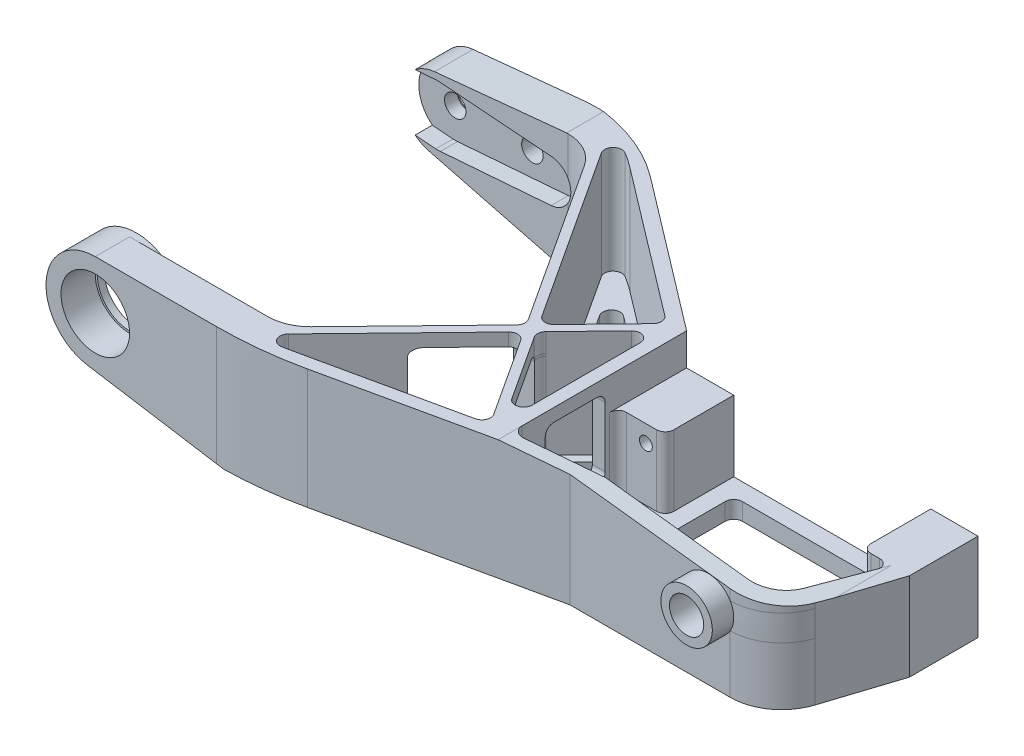
SolidWorks part; units mm, degrees
material "ABS"
ref_plane "Front Plane" through (0, 0, 0) normal (0, 0, 1) x (1, 0, 0)
ref_plane "Top Plane" through (0, 0, 0) normal (0, 1, 0) x (1, 0, 0)
ref_plane "Right Plane" through (0, 0, 0) normal (1, 0, 0) x (0, 0, -1)
sketch "Sketch1" plane through (0, 0, 0) normal (0, 1, 0) x (1, 0, 0)
  line L0 (0, 0) -> (0, -22)
  line L1 (0, 0) -> (34, 0)
  line L2 (34, 0) -> (34, -22)
  line L3 (34, -22) -> (0, -22)
  line L4 (0, -18) -> (34, -18) construction
  line L5 (6, -16) -> (28, -16) construction
  line L6 (6, -16) -> (6, 8) construction
  line L7 (6, 8) -> (28, 8) construction
  line L8 (28, -16) -> (28, 8) construction
  line L9 (1, 2) -> (33, 2) construction
  line L10 (1, 2) -> (1, 0) construction
  line L11 (1, 0) -> (33, 0) construction
  line L12 (33, 2) -> (33, 0) construction
  line L13 (21.5, 15.5) -> (21.5, -23) construction
  point P13 (17, 2)
  point P14 (17, 8)
  point P15 (17, -16)
  point P16 (17, 0)
  dimension "D1" = 22
  dimension "D2" = 32
  dimension "D3" = 22
  dimension "D4" = 16
  dimension "D5" = 24
  dimension "D6" = 2
  dimension "D7" = 34
  dimension "D8" = 4
  dimension "D9" = 6.5
  dimension "D10" = 15.5
  dimension "D11" = 1
extrude "Boss-Extrude1" add sketch "Sketch1" along normal blind 2
sketch "Sketch2" plane through (0, 2, 0) normal (0, 1, 0) x (1, 0, 0)
  line L0 (34, -22) -> (34, 0) construction
  line L1 (0, 0) -> (5.5, 0)
  line L2 (0, 0) -> (0, -8)
  line L3 (0, -8) -> (5.5, -8)
  line L4 (5.5, 0) -> (5.5, -8)
  line L5 (34, 0) -> (28.5, 0)
  line L6 (34, 0) -> (34, -8)
  line L7 (34, -8) -> (28.5, -8)
  line L8 (28.5, 0) -> (28.5, -8)
  line L9 (0, -22) -> (34, -22)
  line L10 (0, -22) -> (0, -18)
  line L11 (0, -18) -> (34, -18)
  line L12 (34, -22) -> (34, -18)
  dimension "D1" = 5.5
  dimension "D2" = 4
  dimension "D3" = 8
  dimension "D4" = 23
extrude "Boss-Extrude2" add sketch "Sketch2" along normal blind 12
sketch "Sketch3" plane through (0, 0, 22) normal (0, 0, 1) x (1, 0, 0)
  line L0 (28.5, 14) -> (28.5, 2) construction
  line L1 (34, 2) -> (0, 2) construction
  circle A0 centre (23, 8.25) radius 3
  dimension "D1" = 5.5
  dimension "D2" = 6.25
  dimension "D3" = 6
extrude "Boss-Extrude3" add sketch "Sketch3" along normal blind 1
sketch "Sketch4" plane through (0, 0, 23) normal (0, 0, 1) x (1, 0, 0)
  circle A0 centre (23, 8.25) radius 2
  circle A1 centre (23, 8.25) radius 3 construction
  dimension "D1" = 4
extrude "Cut-Extrude1" cut sketch "Sketch4" against normal blind 11
sketch "Sketch5" plane through (0, 0, 0) normal (0, 0, -1) x (-1, 0, 0)
  line L0 (-17, 13.8331) -> (-17, 2) construction
  line L1 (-28.5, 2) -> (-5.5, 2) construction
  circle A0 centre (-30.75, 8.25) radius 0.75
  circle A1 centre (-3.25, 8.25) radius 0.75
  circle A2 centre (-23, 8.25) radius 2 construction
  circle A3 centre (-23, 8.25) radius 2 construction
  dimension "D1" = 1.5
  dimension "D2" = 27.5
  dimension "D3" = 13.75
extrude "Cut-Extrude2" cut sketch "Sketch5" against normal blind 11
sketch "Sketch7" plane through (0, 0, 0) normal (0, -1, 0) x (1, 0, 0)
  line L0 (-50.5, 23) -> (-27, 23)
  line L1 (-27, 23) -> (-27, -15)
  line L2 (-27, -15) -> (-50.5, -15)
  line L3 (-43.5, 33.241) -> (-43.5, -32.1535) construction
  line L4 (21.5, -15.5) -> (21.5, 23) construction
  line L5 (-50.5, 23) -> (-50.5, 27)
  line L6 (-50.5, 27) -> (-23, 27)
  line L7 (-23, 27) -> (0, 22)
  line L8 (0, 0) -> (-23, -17.5)
  line L9 (-23, -17.5) -> (-50.5, -17.5)
  line L10 (-50.5, -17.5) -> (-50.5, -15)
  line L11 (0, 22) -> (0, 0)
  dimension "D1" = 65
  dimension "D2" = 16.5
  dimension "D3" = 4
  dimension "D4" = 7
  dimension "D5" = 4
  dimension "D6" = 2.5
  dimension "D7" = 44.5
extrude "Boss-Extrude4" add sketch "Sketch7" against normal blind 14
sketch "Sketch8" plane through (0, 0, -17.5) normal (0, 0, -1) x (-1, 0, 0)
  circle A0 centre (42, 8.25) radius 1.25
  circle A1 centre (-23, 8.25) radius 2 construction
  circle A2 centre (-23, 8.25) radius 2 construction
  circle A3 centre (33, 8.25) radius 1.25
  dimension "D1" = 65
  dimension "D2" = 2.5
  dimension "D3" = 9
extrude "Cut-Extrude3" cut sketch "Sketch8" against normal blind 14
sketch "Sketch9" plane through (0, 0, 27) normal (0, 0, 1) x (1, 0, 0)
  circle A0 centre (-42, 8.25) radius 4
  circle A2 centre (-42, 8.25) radius 1.25 construction
  dimension "D1" = 8
extrude "Cut-Extrude4" cut sketch "Sketch9" against normal blind 14
sketch "Sketch10" plane through (0, 0, -15) normal (0, 0, 1) x (1, 0, 0)
  line L0 (-27, 14) -> (-42.4171, 12.4795)
  line L1 (-27, 0) -> (-43.0595, 4.1342)
  line L2 (-27, 14) -> (-50.5, 14)
  line L3 (-50.5, 14) -> (-50.5, 0)
  line L4 (-50.5, 0) -> (-27, 0)
  arc A0 (-42.4171, 12.4795) -> (-43.0595, 4.1342) centre (-42, 8.25) ccw
  circle A1 centre (-42, 8.25) radius 1.25 construction
  dimension "D1" = 3
extrude "Cut-Extrude5" cut sketch "Sketch10" against normal blind 14
sketch "Sketch11" plane through (0, 0, 23) normal (0, 0, -1) x (-1, 0, 0)
  line L0 (50.5, 14) -> (27, 14) construction
  line L1 (27, 0) -> (42.9178, 2.5737)
  line L2 (42, 14) -> (53.108, 14)
  line L3 (53.108, 14) -> (50.7525, 0)
  line L4 (50.7525, 0) -> (27, 0)
  arc A0 (42.9178, 2.5737) -> (42, 14) centre (42, 8.25) ccw
  dimension "D1" = 10
extrude "Cut-Extrude6" cut sketch "Sketch11" against normal blind 14
sketch "Sketch12" plane through (0, 14, 0) normal (0, 1, 0) x (1, 0, 0)
  line L0 (0, 0.013) -> (0, -22) construction
  line L1 (0, -22) -> (-23, -27) construction
  line L2 (-23, -27) -> (-27, -27) construction
  line L3 (-23, -27) -> (-42, -27) construction
  line L4 (-27, -27) -> (-27, 17.5) construction
  line L5 (-27, 17.5) -> (-23, 17.5) construction
  line L6 (-23, 17.5) -> (0, 0.013) construction
  line L7 (-27, -23) -> (-27, 15) construction
  line L8 (-1.5, -0.7308) -> (-1.5, -20.7911)
  line L9 (-1.5, -20.7911) -> (-23.1612, -25.5)
  line L10 (-23.1612, -25.5) -> (-25.5, -25.5)
  line L11 (-25.5, -25.5) -> (-25.5, 16)
  line L12 (-25.5, 16) -> (-23.5055, 16)
  line L13 (-23.5055, 16) -> (-1.5, -0.7308)
  line L14 (0, -8) -> (0, -18) construction
  dimension "D1" = 1.5
extrude "Cut-Extrude7" cut sketch "Sketch12" against normal offset from surface (12.5 mm away) 1.5 up to face at (-8.6, 0, 7.1)
sketch "Sketch13" plane through (0, 1.5, 0) normal (0, 1, 0) x (1, 0, 0)
  line L0 (-1.5, -0.7308) -> (-25.5, -25.5) construction
  line L1 (-25.5, 16) -> (-25.5, -25.5) construction
  line L2 (-25.5, -25.5) -> (-23.1612, -25.5) construction
  line L3 (-1.0812, -20.5179) -> (-25.0812, 16.2732)
  line L4 (-1.5, -20.7911) -> (-25.5, 16) construction
  line L5 (-1.8591, -0.3829) -> (-25.8591, -25.1521)
  line L6 (-1.9188, -21.0642) -> (-25.9188, 15.7268)
  line L7 (-1.1409, -1.0788) -> (-25.1409, -25.8479)
  line L8 (-25.9188, 15.7268) -> (-25.0812, 16.2732)
  line L9 (-25.1409, -25.8479) -> (-25.8591, -25.1521)
  line L10 (-1.0812, -20.5179) -> (-1.9188, -21.0642)
  line L11 (-1.1409, -1.0788) -> (-1.8591, -0.3829)
  line M3 (-1.5, -0.7308) -> (-23.5055, 16)
  line M4 (-23.5055, 16) -> (-25.5, 16)
  line M5 (-25.5, 16) -> (-25.5, -25.5)
  line M6 (-25.5, -25.5) -> (-23.1612, -25.5)
  line M7 (-23.1612, -25.5) -> (-1.5, -20.7911)
  line M8 (-1.5, -20.7911) -> (-1.5, -0.7308)
  dimension "D1" = 0.5
  dimension "D2" = 0.5
extrude "Boss-Extrude5" add sketch "Sketch13" along normal up to surface (12.5 mm away) contours L7 L6 L5 M5 M6 | L7 L3 L5 L6 | L3 L7 L6 M7 M8 | L7 L5 L3 M8 M3 | L6 L5 L3 M4 M5 region at (-5.3366, 1.5, 14.9136) region at (-9.3207, 1.5, 8.8022) region at (-5.2827, 1.5, 4.6322) region at (-17.4756, 1.5, -3.7001) region at (-17.5025, 1.5, 17.2452) up to face at (-16.7778, 14, 6.7536)
sketch "Sketch14" plane through (0, 1.5, 0) normal (0, 1, 0) x (1, 0, 0)
  line L0 (-25.5, -24.7815) -> (-25.5, 15.0849) construction
  line L1 (-25.5, 15.0849) -> (-9.9576, -8.741) construction
  line L2 (-9.9576, -8.741) -> (-25.5, -24.7815) construction
  line L3 (-2.0228, -20.9047) -> (-9.3974, -9.5998) construction
  line L4 (-9.3974, -9.5998) -> (-24.8038, -25.5) construction
  line L5 (-24.8038, -25.5) -> (-23.1612, -25.5) construction
  line L6 (-23.1612, -25.5) -> (-2.0228, -20.9047) construction
  line L7 (-1.5, -19.8759) -> (-1.5, -1.4494) construction
  line L8 (-1.5, -1.4494) -> (-8.6838, -8.8634) construction
  line L9 (-8.6838, -8.8634) -> (-1.5, -19.8759) construction
  line L10 (-9.2441, -8.0046) -> (-24.903, 16) construction
  line L11 (-24.903, 16) -> (-23.5055, 16) construction
  line L12 (-23.5055, 16) -> (-1.9009, -0.426) construction
  line L13 (-1.9009, -0.426) -> (-9.2441, -8.0046) construction
  line L14 (-24.5, -22.3124) -> (-24.5, 11.7216)
  line L15 (-24.5, 11.7216) -> (-11.2314, -8.6186)
  line L16 (-11.2314, -8.6186) -> (-24.5, -22.3124)
  line L17 (-3.6532, -20.2358) -> (-9.5507, -11.1951)
  line L18 (-9.5507, -11.1951) -> (-22.2219, -24.2725)
  line L19 (-22.2219, -24.2725) -> (-22.2219, -24.2725)
  line L20 (-22.2219, -24.2725) -> (-3.6532, -20.2358)
  line L21 (-2.5, -16.5127) -> (-2.5, -3.9185)
  line L22 (-2.5, -3.9185) -> (-7.41, -8.9858)
  line L23 (-7.41, -8.9858) -> (-2.5, -16.5127)
  line L24 (-9.0908, -6.4093) -> (-22.2836, 13.8148)
  line L25 (-22.2836, 13.8148) -> (-22.2836, 13.8148)
  line L26 (-22.2836, 13.8148) -> (-3.4035, -0.5398)
  line L27 (-3.4035, -0.5398) -> (-9.0908, -6.4093)
  dimension "D1" = 1
extrude "Cut-Extrude8" cut sketch "Sketch14" against normal blind 1.5
sketch "Sketch21" plane through (0, 0, -15) normal (0, 0, 1) x (1, 0, 0)
  line L0 (-29, 8.25) -> (-42, 8.25) construction
  line L1 (-42, 8.25) -> (-55, 8.25) construction
  line L2 (-28.8077, 5.7574) -> (-41.7308, 4.7604)
  line L3 (-28.8077, 10.7426) -> (-41.7308, 11.7396)
  line L4 (-42.2692, 11.7396) -> (-55.1923, 10.7426)
  line L5 (-27, 0) -> (-27, 14)
  line L6 (-55.1923, 5.7574) -> (-42.2692, 4.7604)
  line L7 (-27, 14) -> (-27, 0) construction
  line L8 (-27, 14) -> (-42.4171, 12.4795)
  line L10 (-43.0595, 4.1342) -> (-27, 0)
  arc A0 (-41.7308, 11.7396) -> (-42.2692, 11.7396) centre (-42, 8.25) ccw
  arc A1 (-28.8077, 5.7574) -> (-28.8077, 10.7426) centre (-29, 8.25) ccw
  arc A2 (-55.1923, 10.7426) -> (-55.1923, 5.7574) centre (-55, 8.25) ccw
  arc A3 (-42.2692, 4.7604) -> (-41.7308, 4.7604) centre (-42, 8.25) ccw
  arc A4 (-43.0595, 4.1342) -> (-42.4171, 12.4795) centre (-42, 8.25) cw
  line M11 (-27, 14) -> (-42.4171, 12.4795)
  arc M12 (-42.4171, 12.4795) -> (-43.0595, 4.1342) centre (-42, 8.25) ccw
  line M13 (-43.0595, 4.1342) -> (-27, 0)
  line M14 (-27, 0) -> (-27, 14)
  dimension "D1" = 13
  dimension "D2" = 7
  dimension "D3" = 5
extrude "Boss-Extrude7" add sketch "Sketch21" along normal blind 2 contours A3 L6 A1 L2 M12 M13 M14 | A1 L4 A0 L3 M14 M11 M12 region at (-32.8976, 3.5101, -15) region at (-33.2832, 12.2017, -15)
fillet "Fillet2" radius 45 2 edges at (-23, 7, 27) (0, 7, 22)
fillet "Fillet3" radius 20 1 edges at (-23, 7, -17.5)
sketch "Sketch19" plane through (0, 2, 0) normal (0, 1, 0) x (1, 0, 0)
  line L0 (28.5, 0) -> (5.5, 0) construction
  line L1 (5.5, 0) -> (0, 0) construction
  line L2 (5.5, -8) -> (5.5, 0) construction
  line L3 (5.5, 0) -> (5.5, -18) construction
  line L4 (34, -18) -> (0, -18) construction
  line L5 (5.5, -18) -> (28.5, -18) construction
  line L6 (28.5, -18) -> (28.5, 0) construction
  line L7 (26.5, -2) -> (7.5, -2)
  line L8 (7.5, -2) -> (7.5, -16)
  line L9 (7.5, -16) -> (26.5, -16)
  line L10 (26.5, -16) -> (26.5, -2)
  dimension "D1" = 2
extrude "Cut-Extrude11" cut sketch "Sketch19" against normal through all
sketch "Sketch20" plane through (0, 0, 0) normal (1, 0, 0) x (0, 0, -1)
  line L0 (-8, 2) -> (-18, 2) construction
  line L1 (-18, 2) -> (-18, 14) construction
  line L2 (-18, 14) -> (-8, 14) construction
  line L3 (-8, 14) -> (-8, 2) construction
  line L4 (-9.5, 3.5) -> (-16.5, 3.5)
  line L5 (-16.5, 3.5) -> (-16.5, 12.5)
  line L6 (-16.5, 12.5) -> (-9.5, 12.5)
  line L7 (-9.5, 12.5) -> (-9.5, 3.5)
  dimension "D1" = 1.5
extrude "Cut-Extrude12" cut sketch "Sketch20" against normal blind 31.6667
fillet "Fillet4" radius 20 2 edges at (-23.5055, 7.75, -16) (-23.1612, 7.75, 25.5)
fillet "Fillet6" radius 1 18 edges at (-0.75, 12.5, 9.5) (-9.4808, 12.5, 9.5) (-26.25, 12.5, 9.5) (-0.75, 3.5, 9.5) (-9.4808, 3.5, 9.5) (-26.25, 3.5, 9.5) (-26.25, 12.5, 16.5) (-16.7795, 12.5, 16.5) (-0.75, 12.5, 16.5) (-4.2992, 12.5, 16.5) (-26.25, 3.5, 16.5) (-16.7795, 3.5, 16.5) (-4.2992, 3.5, 16.5) (-0.75, 3.5, 16.5) (26.5, 1, 16) (26.5, 1, 2) (7.5, 1, 2) (7.5, 1, 16)
sketch "Sketch22" plane through (0, 0, 23) normal (0, 0, -1) x (-1, 0, 0)
  circle A0 centre (42, 8.25) radius 3.75
  circle A1 centre (42, 8.25) radius 5.75
  dimension "D1" = 7.5
extrude "Boss-Extrude8" add sketch "Sketch22" along normal blind 0.8
sketch "Sketch23" plane through (0, 0, 0) normal (0, 0, -1) x (-1, 0, 0)
  line L0 (0, 14) -> (0, 0) construction
  line L1 (-34, 14) -> (0, 14)
  line L2 (-34, 14) -> (-34, 10.25)
  line L3 (-34, 10.25) -> (0, 10.25)
  line L4 (0, 14) -> (0, 10.25)
  circle A0 centre (-30.75, 8.25) radius 0.75 construction
  dimension "D1" = 2
extrude "Cut-Extrude13" cut sketch "Sketch23" against normal blind 10.8
sketch "Sketch24" plane through (0, 0, 0) normal (0, -1, 0) x (1, 0, 0)
  line L0 (46.689, 6) -> (-57.6039, 6) construction
  line L1 (-27.8348, 27) -> (-42, 27) construction
  line L2 (-29.7436, -17.5) -> (-42.4171, -17.5) construction
  line L3 (26, 23) -> (20, 23) construction
  dimension "D1" = 21
  dimension "D2" = 23.5
  dimension "D3" = 17
sketch "Sketch25" plane through (0, 0, 22) normal (0, 0, 1) x (1, 0, 0)
  line L4 (4.8348, 0) -> (34, 0) construction
  line L5 (14, 0) -> (14, 14)
  line L12 (14, 14) -> (34, 14)
  line L13 (34, 14) -> (34, 0)
  line L14 (34, 0) -> (14, 0)
  line L15 (4.8348, 14) -> (34, 14) construction
  circle A0 centre (23, 8.25) radius 3
  circle A3 centre (23, 8.25) radius 3 construction
  point P4 (2.5, 12.076)
  point P9 (6.5, 14)
  circle M8 centre (23, 8.25) radius 3
  line M9 (4.8348, 0) -> (34, 0)
  line M14 (4.8348, 14) -> (4.8348, 0)
  dimension "D2" = 20
extrude "Cut-Extrude14" cut sketch "Sketch25" against normal offset from surface 2.5 and the other way blind 10 contours L5 M9 M14 M8 | M14 region at (14.2441, 7, 22) up to face at (25, 8.25, 23)
sketch "Sketch28" plane through (0, 0, -17.5) normal (0, 0, -1) x (-1, 0, 0)
  circle A0 centre (42, 8.25) radius 2.5
  dimension "D1" = 5
extrude "Cut-Extrude16" cut sketch "Sketch28" against normal blind 1
sketch "Sketch29" plane through (0, 14, 0) normal (0, 1, 0) x (1, 0, 0)
  line L0 (-27, -23) -> (-23.7738, -23)
  line L1 (-9.9576, -8.741) -> (-25.5, -24.7815) construction
  line L2 (-23.7738, -23) -> (-24.14, 13)
  line L3 (-9.9576, -8.741) -> (-25.5, 15.0849) construction
  line L4 (-24.14, 13) -> (-27, 13)
  line L5 (-27, 13) -> (-27, -23)
extrude "Cut-Extrude17" cut sketch "Sketch29" against normal blind 20
sketch "Sketch30" plane through (0, 14, 0) normal (0, 1, 0) x (1, 0, 0)
  line L0 (-25.5, -23) -> (-23.7738, -23)
  line L1 (-23.7738, -23) -> (-25.5, -24.7815)
  line L2 (-25.5, -24.7815) -> (-25.5, -23)
  line L3 (-25.5, 15.0849) -> (-25.5, 13)
  line L4 (-25.5, 13) -> (-24.14, 13)
  line L5 (-24.14, 13) -> (-25.5, 15.0849)
extrude "Boss-Extrude9" add sketch "Sketch30" against normal up to surface (12.5 mm away) up to face at (-25.0467, 1.5, -13.695)
sketch "Sketch31" plane through (0, 1.5, 0) normal (0, 1, 0) x (1, 0, 0)
  line L0 (-24.1211, 11.1407) -> (-25.3339, 13)
  line L1 (-24.14, 13) -> (-27, 13) construction
  line L2 (-25.3339, 13) -> (-24.14, 13)
  line L3 (-24.14, 13) -> (-24.1211, 11.1407)
  line L4 (-23.7883, -21.5779) -> (-25.1663, -23)
  line L5 (-42, -23) -> (-23.7738, -23) construction
  line L6 (-25.1663, -23) -> (-23.7738, -23)
  line L7 (-23.7738, -23) -> (-23.7883, -21.5779)
  line L8 (-23.7883, -21.5779) -> (-11.2314, -8.6186) construction
  line L9 (-11.2314, -8.6186) -> (-24.1211, 11.1407) construction
extrude "Boss-Extrude10" add sketch "Sketch31" against normal up to surface (1.5 mm away) up to face at (-8.5891, 0, 9.3708)
fillet "Fillet9" radius 5 2 edges at (-25.1663, 0.75, 23) (-25.3339, 0.75, -13)
fillet "Fillet10" radius 5 2 edges at (-24.14, 7.75, -13) (-23.7738, 7.75, 23)
sketch "Sketch32" plane through (0, 0, -13) normal (0, 0, 1) x (1, 0, 0)
  circle A0 centre (-29, 8.25) radius 2.5
  arc A1 (-28.8077, 5.7574) -> (-27, 6.75) centre (-29, 8.25) ccw construction
extrude "Cut-Extrude18" cut sketch "Sketch32" against normal up to surface (2 mm away) and the other way blind 20 up to face at (-37.0324, 8.25, -15)
sketch "Sketch34" plane through (0, 2, 0) normal (0, 1, 0) x (1, 0, 0)
  line L0 (27, -18.5) -> (32, -18.5)
  line L1 (32, -18.5) -> (32, -8)
  line L2 (34, -8) -> (28.5, -8) construction
  line L3 (32, -8) -> (34, -8)
  line L4 (34, -8) -> (34, 0) construction
  line L5 (27, -18.5) -> (27, -20.5)
  line L6 (27, -20.5) -> (34, -20.5)
  line L7 (34, -18) -> (34, -8) construction
  line L8 (34, -20.5) -> (34, -8)
extrude "Boss-Extrude12" add sketch "Sketch34" along normal up to surface (8.25 mm away) up to face at (31.25, 10.25, 4)
sketch "Sketch36" plane through (0, 10.25, 0) normal (0, 1, 0) x (1, 0, 0)
  line L2 (28.5, -8) -> (32, -8) construction
  line L3 (32, -8) -> (32, -18) construction
  line L4 (32, -18) -> (34, -18)
  line L6 (28.5, -8) -> (28.5, -18)
  line L7 (32, -18) -> (0, -18) construction
  line L8 (28.5, -18) -> (32, -18)
  line L9 (28.5, -8) -> (32, -8)
  line L10 (32, -8) -> (34, -8)
  line L11 (34, -18) -> (34, 0) construction
  line L12 (34, -8) -> (34, -18)
extrude "Boss-Extrude13" add sketch "Sketch36" along normal up to surface (3.75 mm away) and the other way up to surface (8.25 mm away) up to face at (-10.6299, 14, 11.5996) other way up to face at (17, 2, 9)
sketch "Sketch38" plane through (0, 2, 0) normal (0, 1, 0) x (1, 0, 0)
  line L0 (28.5, -8) -> (31.8979, -8)
  line L1 (34, -8) -> (28.5, -8) construction
  line L2 (31.8979, -8) -> (28.5, -18.5)
  line L3 (28.5, -18.5) -> (0, -18.5)
  line L4 (0, -18.5) -> (0, -18)
  line L5 (0, -18) -> (28.5, -18)
  line L6 (28.5, -18) -> (28.5, -8)
  line L7 (34, -8) -> (34, -20.5)
  line L8 (34, -20.5) -> (29.9549, -20.5)
  line L9 (14, -20.5) -> (34, -20.5) construction
  line L10 (29.9549, -20.5) -> (34, -8)
  point P15 (0, 0)
  dimension "D1" = 2
  dimension "D2" = 2
extrude "Cut-Extrude21" cut sketch "Sketch38" along normal blind 20
sketch "Sketch39" plane through (0, 2, 0) normal (0, 1, 0) x (1, 0, 0)
  line L0 (34, -8) -> (29.9549, -20.5)
  line L1 (29.9549, -20.5) -> (34, -20.5)
  line L2 (34, -20.5) -> (34, -8)
extrude "Cut-Extrude22" cut sketch "Sketch39" against normal up to next
fillet "Fillet13" radius 6 1 edges at (29.9549, 7, 20.5)
fillet "Fillet14" radius 4 1 edges at (28.5, 8, 18.5)
sketch "Sketch40" plane through (0, 14, 0) normal (0, 1, 0) x (1, 0, 0)
  line L0 (-4.7245, -23.0271) -> (6.9, -20.5)
  line L1 (-4.7245, -23.0271) -> (-18.2755, -25.9729) construction
  line L2 (14, -20.5) -> (25.5902, -20.5) construction
  line L3 (6.9, -20.5) -> (19.8591, -20.5)
  line L4 (19.8591, -20.5) -> (19.8591, -23.0271)
  line L5 (19.8591, -23.0271) -> (-4.7245, -23.0271)
extrude "Cut-Extrude23" cut sketch "Sketch40" against normal through all
sketch "Sketch41" plane through (0, 14, 0) normal (0, 1, 0) x (1, 0, 0)
  line L0 (0, -18.5) -> (0, -20.465)
  line L1 (0, -20.465) -> (9.0388, -18.5)
  line L2 (9.0388, -18.5) -> (0, -18.5)
  line L3 (25.5902, -18.5) -> (0, -18.5) construction
  line L4 (0, -18.5) -> (25.5902, -18.5) construction
  line L5 (-21.0949, -25.0508) -> (-2.0228, -20.9047) construction
  point P8 (0.1901, -18.5)
extrude "Cut-Extrude24" cut sketch "Sketch41" against normal up to surface (12 mm away) up to face at (17.2594, 2, 9.4834)
sketch "Sketch42" plane through (0, 0, 0) normal (0, 0, -1) x (-1, 0, 0)
  line L1 (0, 14) -> (-34, 14)
  line L2 (-34, 14) -> (-34, 10.25)
  line L3 (-34, 10.25) -> (-28.5, 10.25) construction
  line L4 (-34, 10.25) -> (-34, 0) construction
  line L5 (-34, 10.25) -> (-31.8979, 10.25)
  line L6 (-31.8979, 10.25) -> (0, 14)
extrude "Cut-Extrude25" cut sketch "Sketch42" against normal blind 30
fillet "Fillet8" radius 1 26 edges at (-22.2219, 0.75, 24.2725) (-24.8038, 7.75, 25.5) (-7.41, 0.75, 8.9858) (-8.6838, 7.75, 8.8634) (-1.5, 7.75, 19.8759) (-2.5, 0.75, 16.5127) (-1.5, 7.75, 1.4494) (-2.5, 0.75, 3.9185) (-9.5507, 0.75, 11.1951) (-9.3974, 2.7822, 9.5998) (-2.0228, 7.75, 20.9047) (-3.6532, 0.75, 20.2358) (-9.9576, 7.75, 8.741) (-11.2314, 0.75, 8.6186) (-1.9009, 7.75, 0.426) (-3.4035, 0.75, 0.5398) (-9.0908, 0.75, 6.4093) (-9.2441, 7.75, 8.0046) (-22.2836, 0.75, -13.8148) (-24.903, 7.75, -16) (-9.3974, 12.9678, 9.5998) (28.5, 6.125, 8) (5.5, 6.125, 8) (31.8979, 6.125, 8) (0, 6.125, 8) (0, 8, 20.465)
equation "\"D3@Sketch5\"=\"D2@Sketch5\"/2"
equation "\"D1@Sketch13\"=\"D2@Sketch13\""
